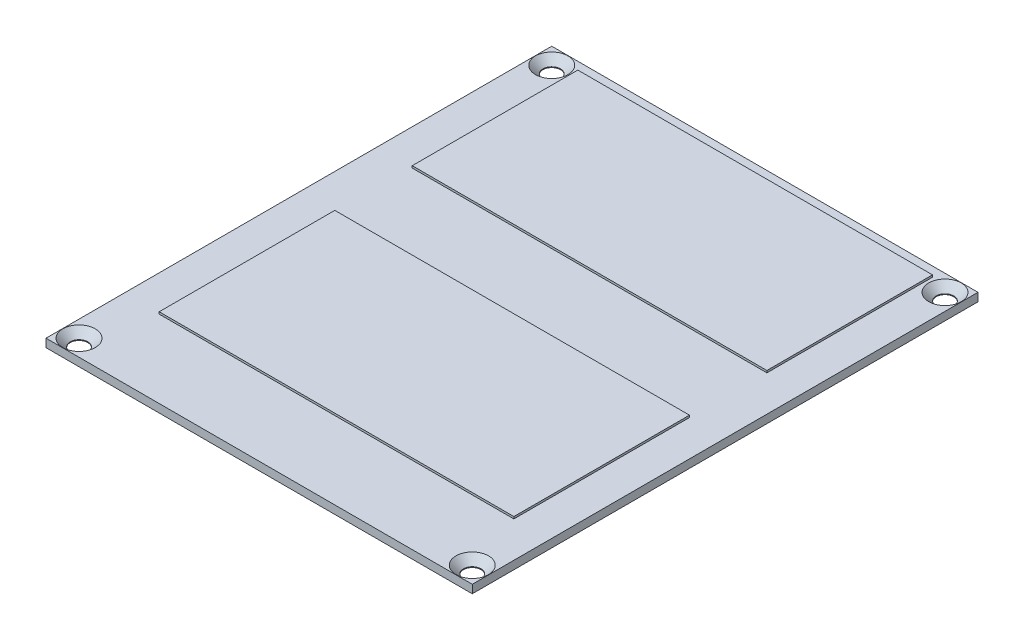
SolidWorks part; units mm, degrees
ref_plane "Front" through (0, 0, 0) normal (0, 0, 1) x (1, 0, 0)
ref_plane "Top" through (0, 0, 0) normal (0, 1, 0) x (1, 0, 0)
ref_plane "Right" through (0, 0, 0) normal (1, 0, 0) x (0, 0, -1)
sketch "Sketch1" plane through (0, 0, 0) normal (0, 1, 0) x (1, 0, 0)
  line L0 (-38.1, 45.8) -> (38.1, 45.8) construction
  line L1 (-41.3, 49) -> (41.3, 49)
  line L2 (-41.3, 49) -> (-41.3, -49)
  line L3 (-41.3, -49) -> (41.3, -49)
  line L4 (41.3, 49) -> (41.3, -49)
  line L5 (-41.3, 49) -> (41.3, -49) construction
  line L6 (-41.3, -49) -> (41.3, 49) construction
  line L7 (38.1, 45.8) -> (38.1, -45.8) construction
  line L8 (-38.1, -45.8) -> (38.1, -45.8) construction
  line L9 (-38.1, 45.8) -> (-38.1, -45.8) construction
  line L11 (-14.8727, -36.2) -> (4.9273, -36.2)
  line L12 (-14.8727, -36.2) -> (-14.8727, -39.9)
  line L13 (-14.8727, -39.9) -> (4.9273, -39.9)
  line L14 (4.9273, -36.2) -> (4.9273, -39.9)
  line L15 (-14.8727, -36.2) -> (4.9273, -39.9) construction
  line L16 (-14.8727, -39.9) -> (4.9273, -36.2) construction
  line L17 (6.4273, -36.2) -> (24.1, -36.2)
  line L18 (6.4273, -36.2) -> (6.4273, -39.9)
  line L19 (6.4273, -39.9) -> (24.1, -39.9)
  line L20 (24.1, -36.2) -> (24.1, -39.9)
  line L21 (6.4273, -36.2) -> (24.1, -39.9) construction
  line L22 (6.4273, -39.9) -> (24.1, -36.2) construction
  line L23 (8.5108, -31) -> (24.1, -31)
  line L24 (8.5108, -31) -> (8.5108, -34.7)
  line L25 (8.5108, -34.7) -> (24.1, -34.7)
  line L26 (24.1, -31) -> (24.1, -34.7)
  line L27 (8.5108, -31) -> (24.1, -34.7) construction
  line L28 (8.5108, -34.7) -> (24.1, -31) construction
  circle A0 centre (-38.1, 45.8) radius 1.6
  circle A1 centre (-38.1, -45.8) radius 1.6
  circle A2 centre (38.1, 45.8) radius 1.6
  circle A3 centre (38.1, -45.8) radius 1.6
  point P0 (0, 0)
  point P14 (-4.9727, -38.05)
  point P19 (15.2637, -38.05)
  point P24 (16.3054, -32.85)
  point P29 (6.4273, -38.05)
  dimension "D4" = 3.2
  dimension "D1" = 82.6
  dimension "D2" = 98
  dimension "D5" = 1.5
  dimension "D6" = 3.7
  dimension "D7" = 9.1
  dimension "D8" = 19.8
  dimension "D9" = 1.5
  dimension "D10" = 17.2
  dimension "D3" = 3.2
extrude "Boss-Extrude1" add sketch "Sketch1" along normal blind 1.6 contours L26 L23 L24 L25 | L20 L17 L18 L19 | L4 L1 L2 L3 A3 A2 A1 A0 L11 L14 L13 L12 L17 L20 L19 L18 L23 L26 L25 L24 | L14 L11 L12 L13 region at (-0.2001, 0, -0.9115) region at (-4.9727, 0, 38.05) region at (15.2637, 0, 38.05) region at (16.3054, 0, 32.85)
extrude "Boss-Extrude2" add sketch "Sketch1<3>" against normal blind 1.6 contours L20 L17 L18 L19 | L26 L23 L24 L25 | L14 L11 L12 L13 region at (-4.9727, 0, 38.05) region at (15.2637, 0, 38.05) region at (16.3054, 0, 32.85)
sketch "Sketch1<3>" plane through (0, 0, 0) normal (0, 1, 0) x (1, 0, 0) same geometry as "Sketch1"
sketch "Sketch2" plane through (0, 1.6, 0) normal (0, 1, 0) x (1, 0, 0)
  line L0 (0, 49) -> (0, -49) construction
  line L1 (-41.3, 49) -> (41.3, 49) construction
  line L2 (-41.3, -49) -> (41.3, -49) construction
  line L4 (-34.3647, 47.1195) -> (34.3647, 47.1195)
  line L5 (-34.3647, 47.1195) -> (-34.3647, 15.0294)
  line L6 (-34.3647, 15.0294) -> (34.3647, 15.0294)
  line L7 (34.3647, 47.1195) -> (34.3647, 15.0294)
  line L8 (-34.3647, 47.1195) -> (34.3647, 15.0294) construction
  line L9 (-34.3647, 15.0294) -> (34.3647, 47.1195) construction
  line L10 (-34.3647, 0.0294) -> (34.3647, 0.0294)
  line L11 (-34.3647, 0.0294) -> (-34.3647, -34)
  line L12 (-34.3647, -34) -> (34.3647, -34)
  line L13 (34.3647, 0.0294) -> (34.3647, -34)
  line L14 (-34.3647, 0.0294) -> (34.3647, -34) construction
  line L15 (-34.3647, -34) -> (34.3647, 0.0294) construction
  point P6 (0, 31.0745)
  point P11 (0, -16.9853)
  dimension "D1" = 15
  dimension "D2" = 15
extrude "Boss-Extrude3" add sketch "Sketch2" along normal blind 0.4
hole_wizard "CSK for M3 Flat Head Machine Screw1" positions "Sketch3" profile "Sketch4" countersink size "M3" standard "ANSI Metric"
sketch "Sketch3" plane through (0, 1.6, 0) normal (0, 1, 0) x (1, 0, 0)
  point P0 (-38.1, 45.8)
  point P3 (38.1, 45.8)
  point P6 (38.1, -45.8)
  point P9 (-38.1, -45.8)
sketch "Sketch4" plane through (-38.1, 1.6, -45.8) normal (1, 0, 0) x (0, 0, 1)
  line L0 (0, 0) -> (0, 4.1715)
  line L1 (0, 4.1715) -> (1.7, 3.15)
  line L2 (1.7, 3.15) -> (1.7, 1.45)
  line L3 (1.7, 1.45) -> (3.15, 0)
  line L5 (3.15, 0) -> (0, 0)
  line L6 (-1.7, 1.45) -> (-3.15, 0) construction
  line L10 (0, 4.1715) -> (-1.7, 3.15) construction
  line L11 (0, -6.35) -> (0, 107.95) construction
  dimension "Hole Dia." = 3.4
  dimension "Hole Depth" = 3.15
  dimension "Near C'Sink Dia." = 6.3
  dimension "Near C'Sink Angle" = 90
  dimension "Drill Angle" = 118
